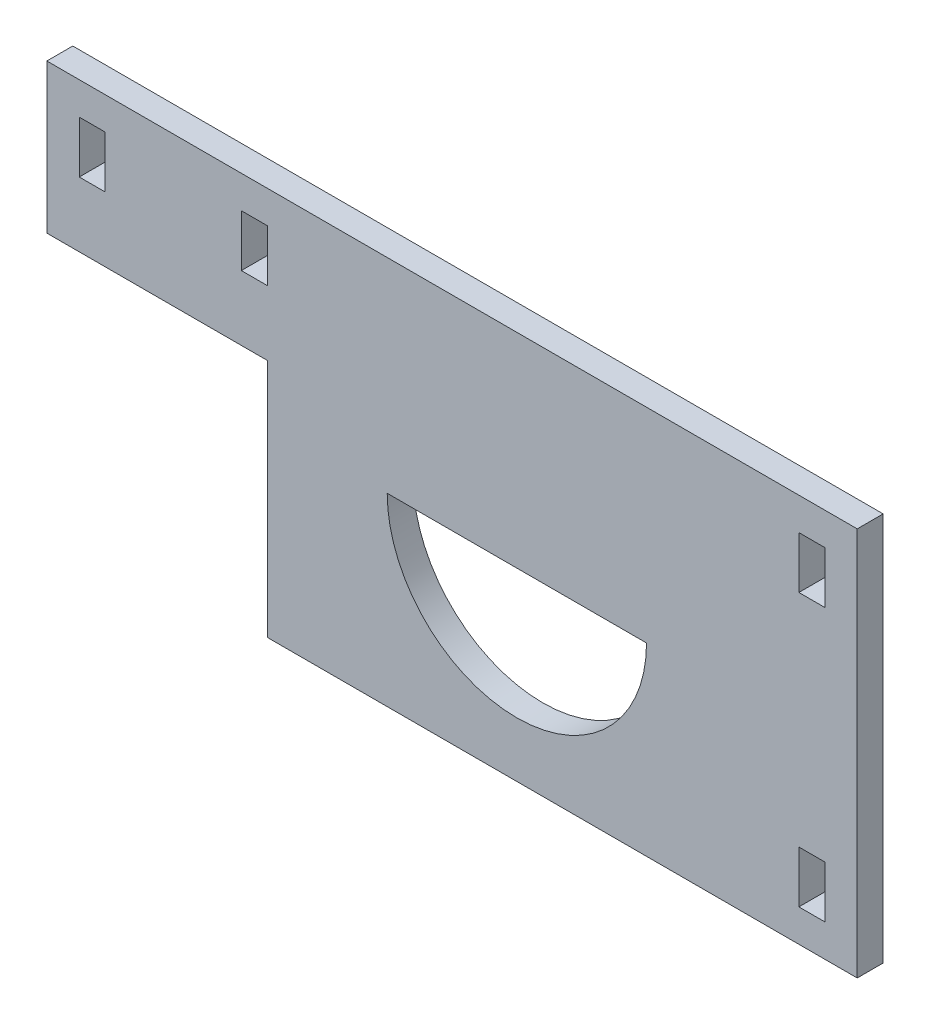
SolidWorks part; units mm, degrees
ref_plane "Front Plane" through (0, 0, 0) normal (0, 0, 1) x (1, 0, 0)
ref_plane "Top Plane" through (0, 0, 0) normal (0, 1, 0) x (1, 0, 0)
ref_plane "Right Plane" through (0, 0, 0) normal (1, 0, 0) x (0, 0, -1)
sketch "Sketch1" plane through (0, 0, 0) normal (0, 0, 1) x (1, 0, 0)
  line L0 (-20, -1.4984) -> (20, -1.4984)
  line L6 (-42.5, 25) -> (-38.5, 25)
  line L9 (-42.5, 25) -> (-42.5, 17)
  line L12 (-42.5, 17) -> (-38.5, 17)
  line L15 (-38.5, 25) -> (-38.5, 17)
  line L21 (-72.5, 30) -> (-72.5, 7)
  line L26 (-72.5, 7) -> (-38.5, 7)
  line L51 (52.5, 30) -> (52.5, -30)
  line L54 (43.5, 25) -> (47.5, 25)
  line L55 (43.5, 25) -> (43.5, 17)
  line L56 (43.5, 17) -> (47.5, 17)
  line L57 (47.5, 25) -> (47.5, 17)
  line L58 (47.5, -17) -> (43.5, -17)
  line L59 (47.5, -17) -> (47.5, -25)
  line L60 (47.5, -25) -> (43.5, -25)
  line L61 (43.5, -17) -> (43.5, -25)
  line L65 (-67.5, 25) -> (-63.5, 25)
  line L66 (-67.5, 25) -> (-67.5, 17)
  line L67 (-67.5, 17) -> (-63.5, 17)
  line L68 (-63.5, 25) -> (-63.5, 17)
  line L73 (-72.5, 30) -> (-72.5, -30) construction
  line L75 (-72.5, -30) -> (52.5, -30) construction
  line L76 (52.5, 30) -> (-72.5, 30)
  line L77 (-38.5, 7) -> (-38.5, -30)
  line L78 (-38.5, -30) -> (52.5, -30)
  arc A12 (-20, -1.4984) -> (20, -1.4984) centre (0, -1.4984) ccw
  point P0 (0, 0)
  point P4 (-65.5, 17)
  point P13 (-38.5, 21)
  point P25 (-63.5, 21)
  dimension "D3" = 4
  dimension "D4" = 8
  dimension "D5" = 21
  dimension "D6" = 60
  dimension "D7" = 10
  dimension "D2" = 82
  dimension "D8" = 20
  dimension "D9" = 20
  dimension "D10" = 0
  dimension "D13" = 5
  dimension "D14" = 5
  dimension "D18" = 5
extrude "Boss-Extrude1" add sketch "Sketch1" along normal blind 4
